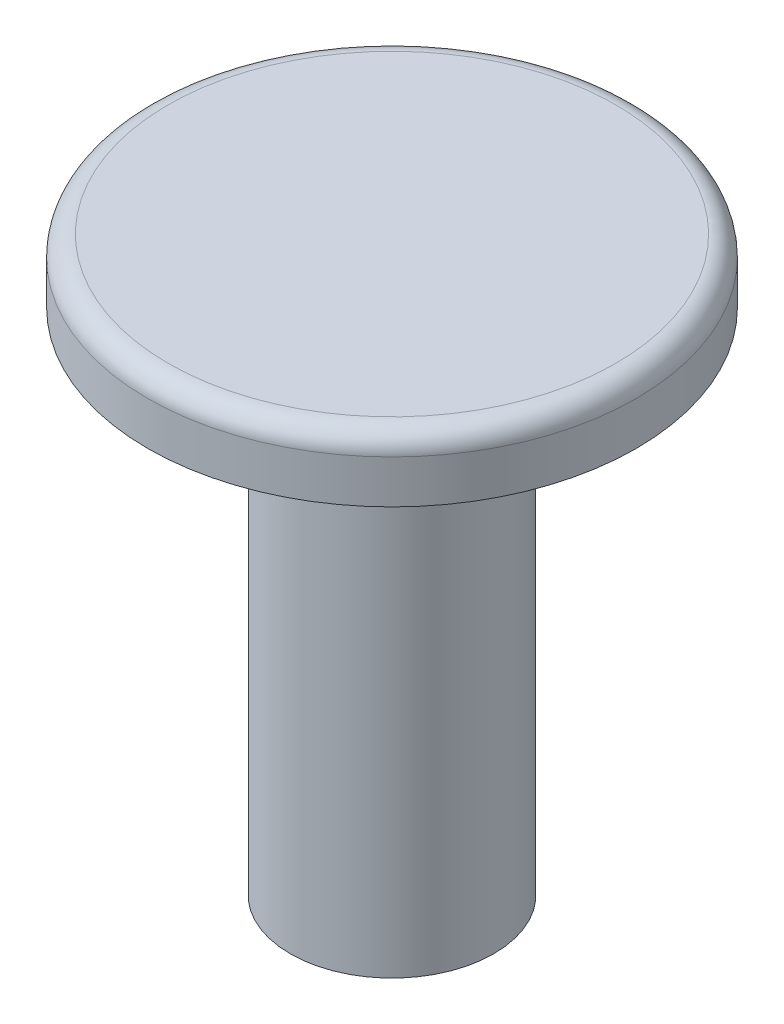
SolidWorks part; units mm, degrees
ref_plane "Front Plane" through (0, 0, 0) normal (0, 0, 1) x (1, 0, 0)
ref_plane "Top Plane" through (0, 0, 0) normal (0, 1, 0) x (1, 0, 0)
ref_plane "Right Plane" through (0, 0, 0) normal (1, 0, 0) x (0, 0, -1)
sketch "Sketch1" plane through (0, 0, 0) normal (0, 1, 0) x (1, 0, 0)
  circle A0 centre (0, 0) radius 2
extrude "Boss-Extrude1" add sketch "Sketch1" along normal blind 10
sketch "Sketch2" plane through (0, 10, 0) normal (0, 1, 0) x (1, 0, 0)
  circle A0 centre (0, 0) radius 4.8
extrude "Boss-Extrude2" add sketch "Sketch2" along normal blind 1.25
fillet "Fillet2" radius 0.4 1 edges at (0, 11.25, 4.8)
ref_axis "Axis1" through (0, 13.6551, 0) along (0, -1, 0)
